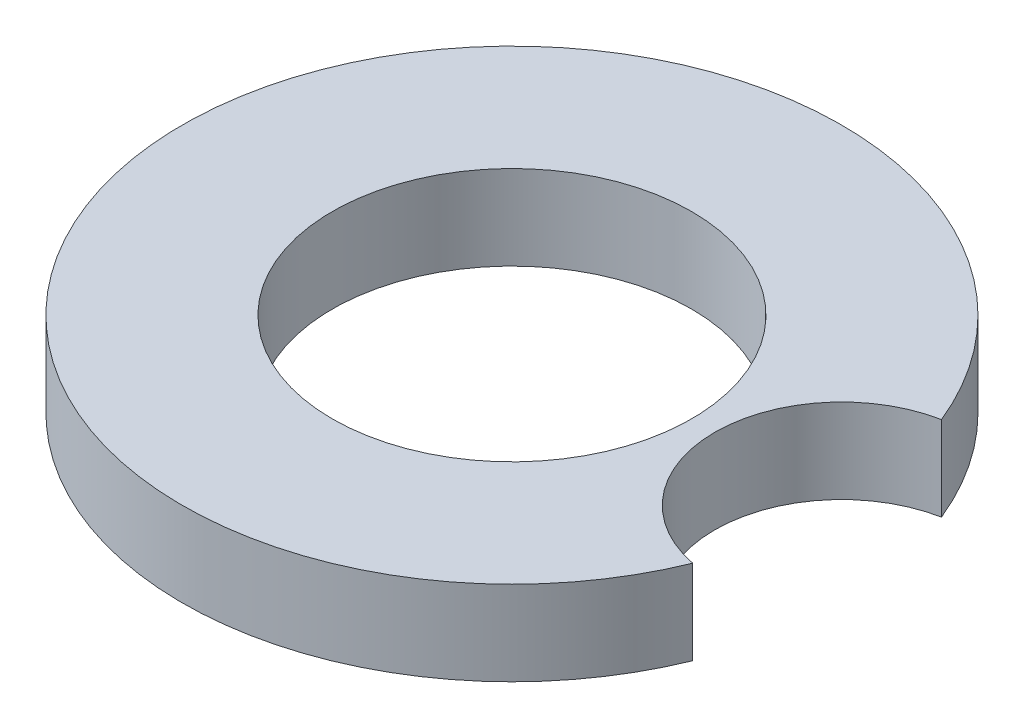
SolidWorks part; units mm, degrees
ref_plane "Front Plane" through (0, 0, 0) normal (0, 0, 1) x (1, 0, 0)
ref_plane "Top Plane" through (0, 0, 0) normal (0, 1, 0) x (1, 0, 0)
ref_plane "Right Plane" through (0, 0, 0) normal (1, 0, 0) x (0, 0, -1)
sketch "Sketch1" plane through (0, 0, 0) normal (0, 1, 0) x (1, 0, 0)
  circle A0 centre (0, 0) radius 27
  circle A1 centre (0, 0) radius 49.53
  dimension "Front_CR_ID" = 54
  dimension "Front_CR_OD" = 99.06
extrude "Boss-Extrude1" add sketch "Sketch1" along normal blind 12.7 contours A1
extrude "Cut-Extrude2" cut sketch "Sketch1<10>" along normal through all contours A0
sketch "Sketch1<10>" plane through (0, 0, 0) normal (0, 1, 0) x (1, 0, 0) same geometry as "Sketch1"
sketch "Sketch2" plane through (0, 12.7, 0) normal (0, 1, 0) x (1, 0, 0)
  circle A2 centre (49.53, 0) radius 19.05
  circle A3 centre (0, 0) radius 49.53 construction
  dimension "D1" = 38.1
extrude "Cut-Extrude3" cut sketch "Sketch2" against normal through all contours A2
ref_plane "Plane1" through (0, 6.35, 0) normal (0, -1, 0) x (-1, 0, 0)
equation "\"Motor_OD\" = 54mm"
equation "\"Aft_Section_Length\" = 32in"
equation "\"Mid_Coupler_Length\" = 12in"
equation "\"AB_Coupler_OD_Length\"= 1in"
equation "\"AB_Coupling_Section_Length\"= 0.375in"
equation "\"AB_Coupler_Length\"= \"AB_Coupler_OD_Length\" + \"AB_Coupling_Section_Length\" * 2"
equation "\"Cutout_Angle\" = 60"
equation "\"AB_Paddle_Height\" = 0.375in"
equation "\"AB_Coupler_Num_Screws\"= 4"
equation "\"Num_Cutouts\" = 4"
equation "\"AB_Coupler_OD\"= 4.024in"
equation "\"AB_Coupler_ID\"= 3.7in"
equation "\"AB_Coupler_Surface_Diameter\"= 3.899in"
equation "\"AB_Coupling_Screw_Diameter\"= 0.1065in"
equation "\"AB_Central_Bushing_Length\" = 0.75in"
equation "\"Lead_Screw_Dist\" = 2in"
equation "\"Lead_Screw_Diam\" = 0.375in"
equation "\"Lead_Screw_Length\" = \"Mid_Coupler_Length\" + 2*0.375in + 2*0.5in"
equation "\"Paddle_Pin_Offset\" = 0.25in"
equation "\"Paddle_Pin_Radius\" = 2.25*2/3in"
equation "\"Paddle_Gear_OD\" = 3.2in"
equation "\"Fwd_BKHD_From_Top\" = 18in"
equation "\"Front_CR_ID@Sketch1\"=\"Motor_OD\""
equation "\"Body_Tube_OD\"= 4.024in"
equation "\"Body_Tube_ID\"= 3.90in"
equation "\"Coupler_OD\" = 3.899in"
equation "\"Coupler_ID\" = 3.755in"
equation "\"Fwd_Section_Length\" = 20in"
equation "\"Mid_Section_Length\" = 4in"
equation "\"Aft_Upper_Tube_Length\" = 10in"
equation "\"Aft_Lower_Tube_Length\" = 18in"
equation "\"Nosecone_Coupler_Length\" = 5in"
equation "\"Avionics_Bulkhead_Thickness\" = 0.25in"
equation "\"Avionics_Bulkhead_Lip\" = 0.125in"
equation "\"Avionics_Board_Length\" = \"Mid_Coupler_Length\" - 2*\"Avionics_Bulkhead_Lip\""
equation "\"Lead_Screw_Hole_Diam\" = 0.386in"
equation "\"Front_CR_OD@Sketch1\"=\"Body_Tube_ID\""
equation "\"Centering_Ring_Cutout_Dia\"=1.5in"
equation "\"D1@Sketch2\"=\"Centering_Ring_Cutout_Dia\""
